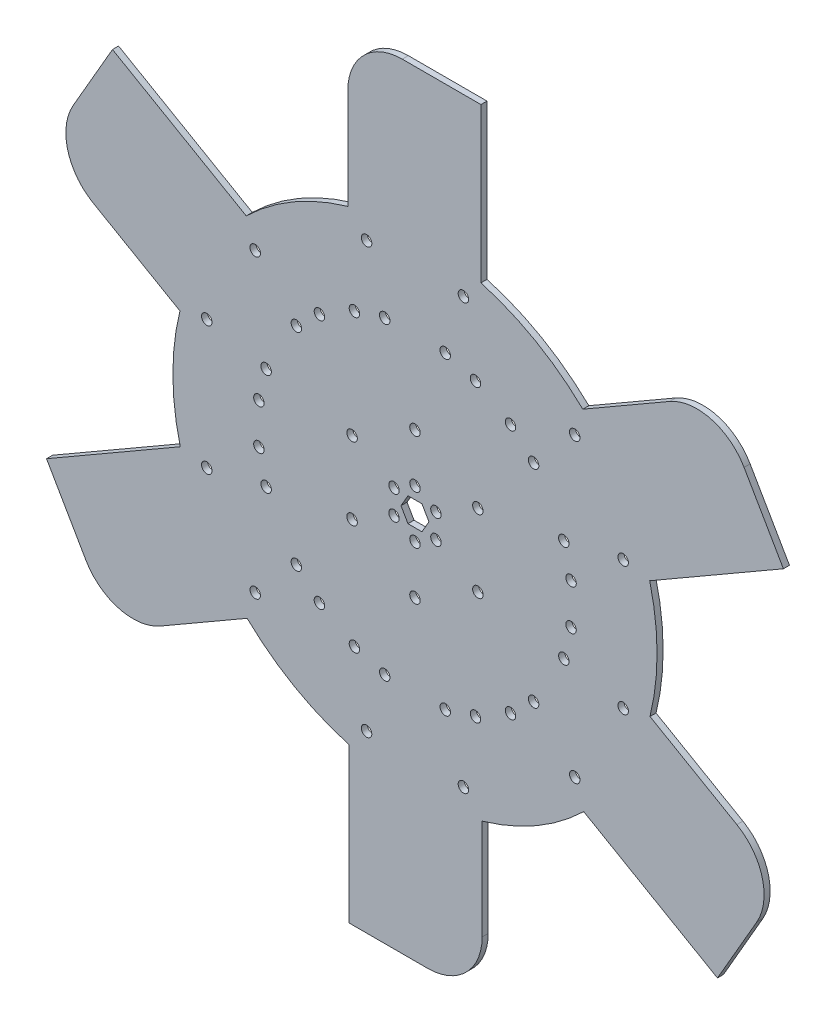
SolidWorks part; units mm, degrees
material "6061 Alloy"
ref_plane "Front Plane" through (0, 0, 0) normal (0, 0, 1) x (1, 0, 0)
ref_plane "Top Plane" through (0, 0, 0) normal (0, 1, 0) x (1, 0, 0)
ref_plane "Right Plane" through (0, 0, 0) normal (1, 0, 0) x (0, 0, -1)
sketch "Sketch1" plane through (0, 0, 0) normal (0, 0, 1) x (1, 0, 0)
  circle A0 centre (0, 0) radius 127
  dimension "D1" = 254
extrude "Boss-Extrude1" add sketch "Sketch1" along normal blind 3.175
sketch "Sketch2" plane through (0, 0, 0) normal (0, 0, 1) x (1, 0, 0)
  line L0 (0, 0) -> (109.9852, 63.5) construction
  line L1 (0, 0) -> (127, 0) construction
  circle A0 centre (0, 0) radius 82.55 construction
  circle A1 centre (0, 0) radius 114.3 construction
  circle A2 centre (0, 0) radius 127 construction
  point P0 (10.9985, 6.35)
  point P3 (78.0935, 26.7564)
  point P5 (50.1161, 65.5963)
  point P6 (81.8661, 10.6037)
  point P7 (109.2116, 33.724)
  point P8 (83.8116, 77.7181)
  point P10 (62.2185, 54.2527)
  point P11 (32.9956, 19.05)
  point P12 (0, 0)
  point P17 (0, 0)
  dimension "D1" = 12.7
  dimension "D3" = 165.1
  dimension "D4" = 228.6
  dimension "D6" = 31.75
  dimension "D2" = 63.5
  dimension "D5" = 50.8
  dimension "D7" = 38.1
  dimension "D8" = 127
  dimension "D9" = 127
  dimension "D10" = 30
ref_axis "Axis1" through (0, 0, -0.1588) along (0, 0, 1)
sketch "Sketch6" plane through (0, 0, 0) normal (0, 0, -1) x (-1, 0, 0)
  line L1 (-49.3399, 69.1809) -> (-133.6084, 117.8334)
  line L2 (-172.6426, 107.3742) -> (-193.2801, 71.629)
  line L3 (-193.2801, 71.629) -> (-84.2649, 8.6891)
  line L4 (-84.2649, 8.6891) -> (-49.3399, 69.1809)
  line L5 (0, 0) -> (-109.9852, 63.5) construction
  arc A0 (-172.6426, 107.3742) -> (-133.6084, 117.8334) centre (-147.8959, 93.0867) cw
  dimension "D5" = 28.575
  dimension "D1" = 69.85
  dimension "8" = 203.2
  dimension "D4" = 35.2425
extrude "Boss-Extrude2" add sketch "Sketch6" against normal up to surface (3.175 mm away) up to face at (127, 0, 3.175)
pattern_circular "CirPattern2" count 6 over 360 about axis through (0, 0, -0.1588) along (0, 0, 1) of "Boss-Extrude2"
sketch "Sketch7" plane through (0, 0, 3.175) normal (0, 0, 1) x (1, 0, 0)
  line L0 (6.6675, -203.2) -> (-34.6075, -203.2) construction
  line L1 (7.3323, 0) -> (3.6662, 6.35)
  line L2 (3.6662, 6.35) -> (-3.6662, 6.35)
  line L3 (-3.6662, 6.35) -> (-7.3323, 0)
  line L4 (-7.3323, 0) -> (-3.6662, -6.35)
  line L5 (-3.6662, -6.35) -> (3.6662, -6.35)
  line L6 (3.6662, -6.35) -> (7.3323, 0)
  line L7 (-172.6426, -107.3742) -> (-193.2801, -71.629) construction
  circle A0 centre (0, 0) radius 6.35 construction
  point P13 (0, 0)
  dimension "D1" = 12.7
extrude "Cut-Extrude1" cut sketch "Sketch7" against normal through all
hole_wizard "M5 Clearance Hole1" positions "Sketch14" profile "Sketch15" hole size "M5" standard "ANSI Metric" end condition through all
sketch "Sketch14" plane through (0, 0, 0) normal (0, 0, -1) x (-1, 0, 0)
  point P0 (-62.2185, 54.2527)
  point P3 (-78.0935, 26.7564)
  point P6 (-81.8661, 10.6037)
  point P9 (-109.2116, 33.724)
  point P12 (-83.8116, 77.7181)
  point P15 (-50.1161, 65.5963)
  point P18 (-32.9956, 19.05)
  point P21 (-10.9985, 6.35)
sketch "Sketch15" plane through (62.2185, 54.2527, 0) normal (1, 0, 0) x (0, 1, 0)
  line L0 (0, 0) -> (0, 3.175)
  line L1 (0, 3.175) -> (2.75, 3.175)
  line L2 (2.75, 3.175) -> (2.75, 0)
  line L5 (2.75, 0) -> (0, 0)
  line L11 (0, -6.35) -> (0, 107.95) construction
  dimension "Thru Hole Dia." = 5.5
  dimension "Thru Hole Depth" = 3.175
pattern_circular "CirPattern3" count 6 over 360 about axis through (0, 0, -0.1588) along (0, 0, 1) of "M5 Clearance Hole1"
